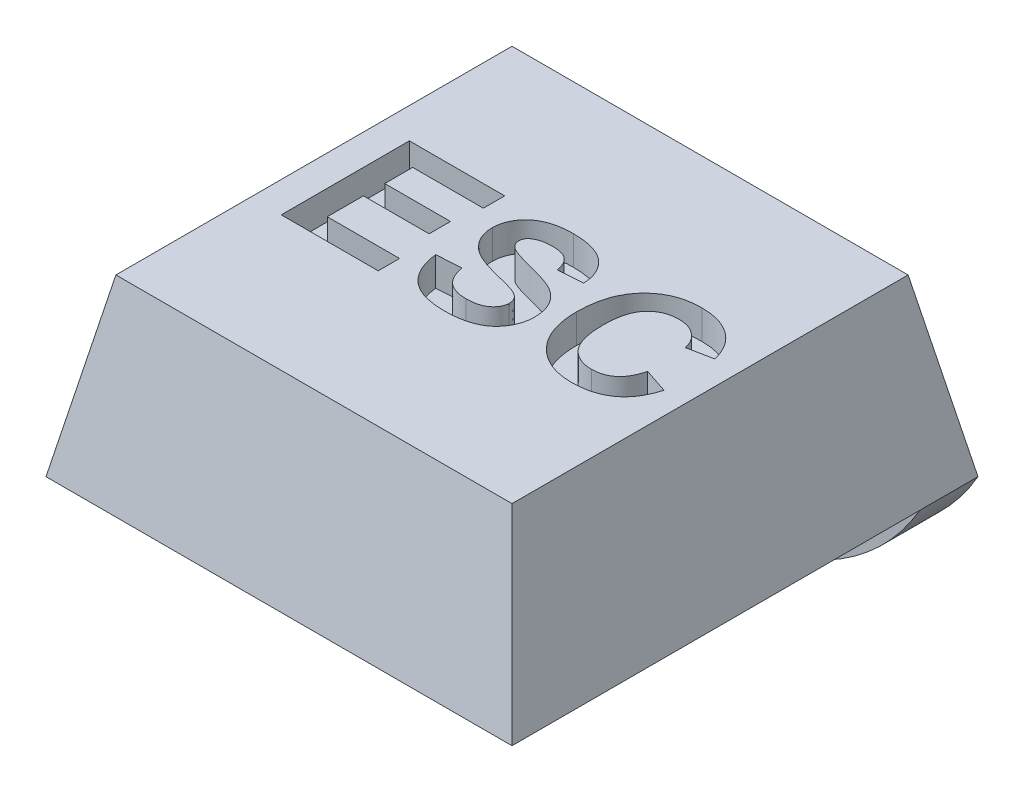
SolidWorks part; units mm, degrees
ref_plane "Front Plane" through (0, 0, 0) normal (0, 0, 1) x (1, 0, 0)
ref_plane "Top Plane" through (0, 0, 0) normal (0, 1, 0) x (1, 0, 0)
ref_plane "Right Plane" through (0, 0, 0) normal (1, 0, 0) x (0, 0, -1)
sketch "Sketch1" plane through (0, 0, 0) normal (0, 1, 0) x (1, 0, 0)
  line L1 (0, 0) -> (8, 0)
  line L2 (0, 0) -> (0, 8)
  line L3 (0, 8) -> (8, 8)
  line L4 (8, 0) -> (8, 8)
  dimension "D1" = 8
  dimension "D2" = 8
extrude "Boss-Extrude1" add sketch "Sketch1" along normal blind 3
sketch "Sketch2" plane through (0, 0, 0) normal (0, 0, 1) x (1, 0, 0)
  line L0 (0, 0) -> (0.6, 3)
  line L1 (0, 3) -> (8, 3) construction
  line L2 (0.6, 3) -> (0, 3)
  line L3 (0, 3) -> (0, 0)
  line L4 (8, 0) -> (7.4, 3)
  line L5 (7.4, 3) -> (8, 3)
  line L6 (8, 3) -> (8, 0)
  dimension "D1" = 0.6
  dimension "D2" = 0.6
extrude "Cut-Extrude1" cut sketch "Sketch2" against normal through all both and the other way through all
sketch "Sketch3" plane through (0, 0, 0) normal (1, 0, 0) x (0, 0, -1)
  line L0 (0, 0) -> (0.6, 3)
  line L1 (8, 3) -> (0, 3) construction
  line L2 (0.6, 3) -> (0, 3)
  line L3 (0, 3) -> (0, 0)
  line L4 (8, 3) -> (7.4, 3)
  line L5 (7.4, 3) -> (8, 0)
  line L6 (8, 3) -> (8, 0)
  dimension "D1" = 0.6
  dimension "D2" = 0.6
extrude "Cut-Extrude2" cut sketch "Sketch3" along normal blind 11
sketch "Sketch4" plane through (0, 0, 0) normal (0, -1, 0) x (1, 0, 0)
  line L0 (8, 0) -> (8, -8) construction
  line L3 (0, 0) -> (8, 0) construction
  circle A0 centre (4, -3.75) radius 1.75
  dimension "D1" = 3.5
  dimension "D2" = 4
  dimension "D3" = 3.75
extrude "Cut-Extrude3" cut sketch "Sketch4" against normal blind 0.4
sketch "Sketch5" plane through (0, 0, 0) normal (0, -1, 0) x (1, 0, 0)
  line L0 (8, 0) -> (8, -8) construction
  line L1 (0, -8) -> (8, -8)
  line L2 (0, -8) -> (0, -7)
  line L3 (0, -7) -> (8, -7)
  line L4 (8, -8) -> (8, -7)
  dimension "D1" = 1
extrude "Boss-Extrude2" add sketch "Sketch5" along normal blind 2
fillet "Fillet1" radius 4 2 edges at (8, -2, -7.5) (0, -2, -7.5)
sketch "Sketch6" plane through (0, 3, 0) normal (0, 1, 0) x (1, 0, 0)
  text T0 "ESC" font "Arial" height 2.2
extrude "Cut-Extrude4" cut sketch "Sketch6" against normal blind 0.5
